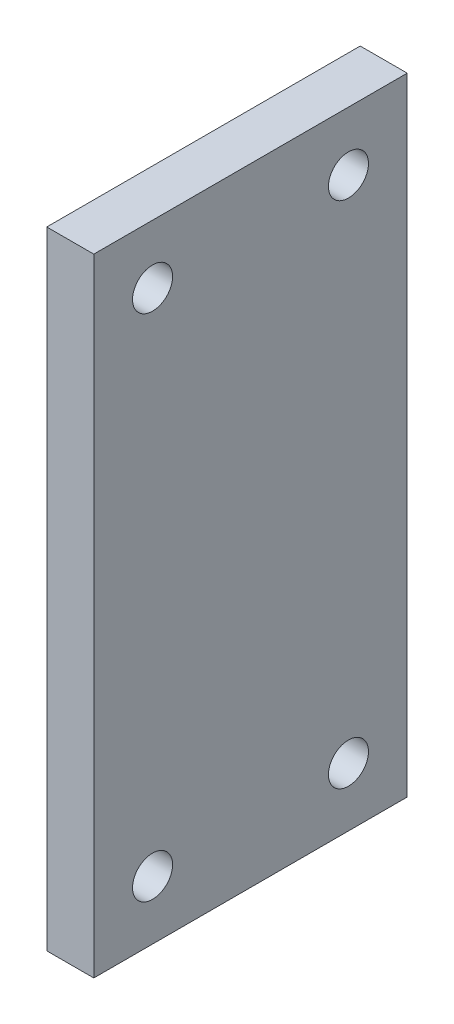
SolidWorks part; units mm, degrees
ref_plane "Front Plane" through (0, 0, 0) normal (1, 0, 0) x (0, 1, 0)
ref_plane "Top Plane" through (0, 0, 0) normal (0, 0, 1) x (0, 1, 0)
ref_plane "Right Plane" through (0, 0, 0) normal (0, 1, 0) x (-1, 0, 0)
sketch "Sketch1" plane through (0, 0, 0) normal (1, 0, 0) x (0, 1, 0)
  line L7 (-40, -20) -> (40, -20)
  line L8 (-40, -20) -> (-40, 20)
  line L9 (-40, 20) -> (40, 20)
  line L10 (40, -20) -> (40, 20)
  line L11 (-40, -20) -> (40, 20) construction
  line L12 (-40, 20) -> (40, -20) construction
  line L13 (-32.5, -12.5) -> (32.5, -12.5) construction
  line L14 (-32.5, -12.5) -> (-32.5, 12.5) construction
  line L15 (-32.5, 12.5) -> (32.5, 12.5) construction
  line L16 (32.5, -12.5) -> (32.5, 12.5) construction
  line L17 (-32.5, -12.5) -> (32.5, 12.5) construction
  line L18 (-32.5, 12.5) -> (32.5, -12.5) construction
  circle A0 centre (-32.5, 12.5) radius 2.555
  circle A1 centre (-32.5, -12.5) radius 2.555
  circle A2 centre (32.5, -12.5) radius 2.555
  circle A3 centre (32.5, 12.5) radius 2.555
  point P0 (0, 0)
  point P2 (0, 0)
  dimension "D5" = 5.11
  dimension "D6" = 5.11
  dimension "D7" = 5.11
  dimension "D8" = 5.11
  dimension "D1" = 80
  dimension "D2" = 40
  dimension "D3" = 65
  dimension "D4" = 25
extrude "Boss-Extrude2" add sketch "Sketch1" along normal blind 6 contours L7 L10 L9 L8
extrude "Cut-Extrude3" cut sketch "Sketch1<3>" along normal up to next contours A0 | A3 | A2 | A1
sketch "Sketch1<3>" plane through (0, 0, 0) normal (1, 0, 0) x (0, 1, 0) same geometry as "Sketch1"
